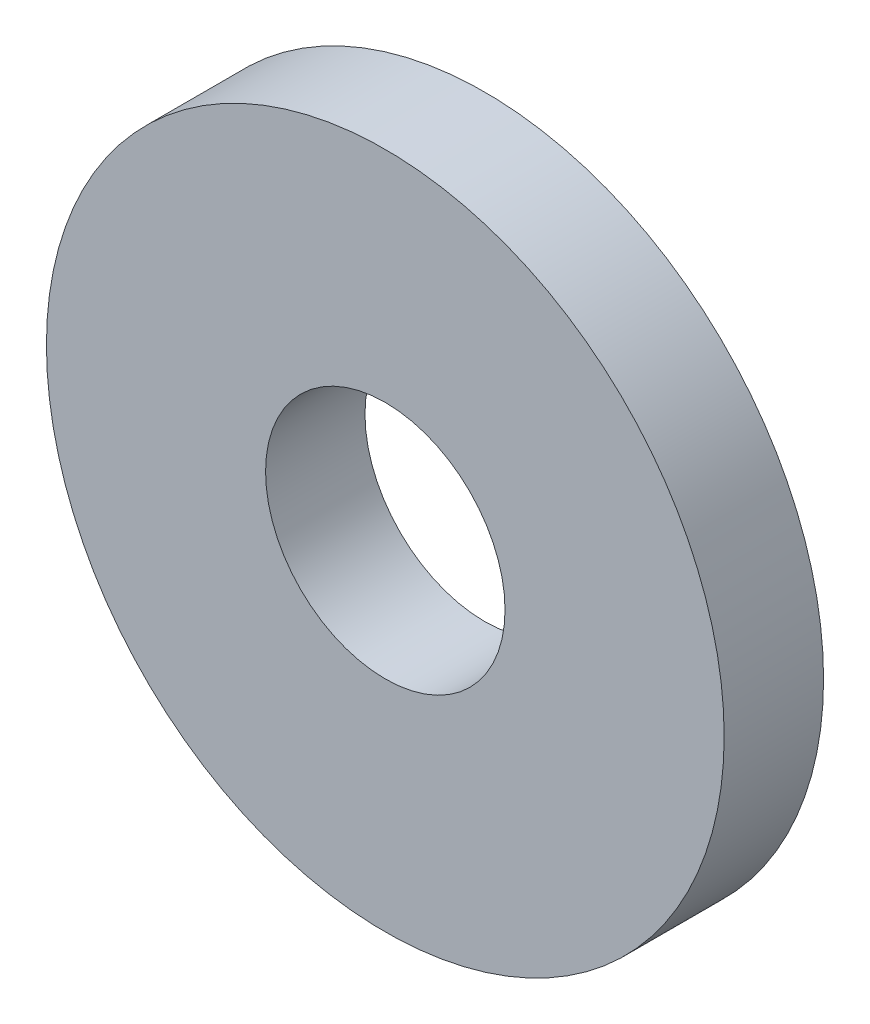
SolidWorks part; units mm, degrees
ref_plane "Front Plane" through (0, 0, 0) normal (0, 0, 1) x (1, 0, 0)
ref_plane "Top Plane" through (0, 0, 0) normal (0, 1, 0) x (1, 0, 0)
ref_plane "Right Plane" through (0, 0, 0) normal (1, 0, 0) x (0, 0, -1)
sketch "Sketch1" plane through (0, 0, 0) normal (0, 0, 1) x (1, 0, 0)
  circle A0 centre (0, 0) radius 7.5 construction
  circle A1 centre (0, 0) radius 2.65 construction
  dimension "OD" = 15
  dimension "ID" = 5.3
sketch "Sketch2" plane through (0, 0, 0) normal (1, 0, 0) x (0, 0, -1)
  line L0 (-1.1, 0) -> (1.1, 0) construction
  line L1 (0, 7.5) -> (0, -7.5) construction
  line L2 (0, 7.5) -> (0, -7.5) construction
  line L3 (-1.1, -7.5) -> (1.1, -7.5) construction
  point P4 (0, 0)
  point P10 (0, -7.5)
  dimension "Thickness" = 2.2
sketch "Sketch3" plane through (0, 0, 0) normal (0, 0, 1) x (1, 0, 0)
  circle A0 centre (0, 0) radius 7.5 construction
  circle A1 centre (0, 0) radius 2.65 construction
  circle A2 centre (0, 0) radius 7.5
  circle A3 centre (0, 0) radius 2.65
extrude "Boss-Extrude1" add sketch "Sketch3" against normal up to vertex (1.1 mm away) and the other way up to vertex (1.1 mm away) up to point (0, 0, -1.1) other way up to point (0, 0, 1.1)
